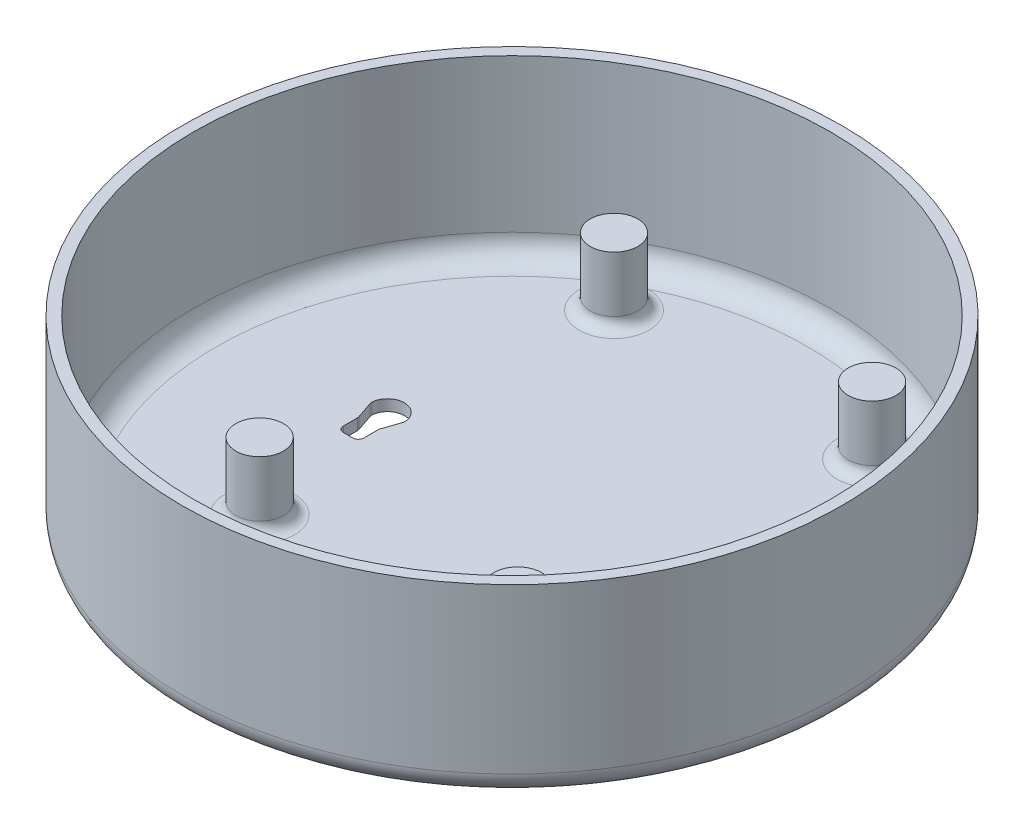
SolidWorks part; units mm, degrees
ref_plane "Front Plane" through (0, 0, 0) normal (0, 0, 1) x (1, 0, 0)
ref_plane "Top Plane" through (0, 0, 0) normal (0, 1, 0) x (1, 0, 0)
ref_plane "Right Plane" through (0, 0, 0) normal (1, 0, 0) x (0, 0, -1)
sketch "Sketch1" plane through (0, 0, 0) normal (0, 1, 0) x (1, 0, 0)
  circle A0 centre (0, 0) radius 29.527
  dimension "D1" = 59.054
extrude "Boss-Extrude1" add sketch "Sketch1" along normal blind 16.698
shell "Shell1" thickness 1 removed face at (0, 16.698, 29.527)
sketch "Sketch4" plane through (0, 0, 0) normal (0, -1, 0) x (1, 0, 0)
  line L0 (0, 29.527) -> (0, -29.527) construction
  line L1 (0, 0) -> (29.527, 0) construction
  line L2 (12.2635, -2.6139) -> (12.8385, -0.925)
  line L3 (15.2635, -2.6139) -> (14.6885, -0.925)
  line L4 (12.8385, -0.925) -> (12.8385, 0.925)
  line L5 (12.8385, 0.925) -> (14.6885, 0.925)
  line L6 (14.6885, 0.925) -> (14.6885, -0.925)
  line L7 (-14.6885, 0.925) -> (-14.6885, -0.925)
  line L8 (-12.8385, 0.925) -> (-14.6885, 0.925)
  line L9 (-12.8385, -0.925) -> (-12.8385, 0.925)
  line L10 (-15.2635, -2.6139) -> (-14.6885, -0.925)
  line L11 (-12.2635, -2.6139) -> (-12.8385, -0.925)
  arc A0 (12.2635, -2.6139) -> (15.2635, -2.6139) centre (13.7635, -2.6139) ccw
  circle A1 centre (0, 0) radius 29.527 construction
  arc A2 (-12.2635, -2.6139) -> (-15.2635, -2.6139) centre (-13.7635, -2.6139) cw
  point P21 (12.8385, 0)
  point P22 (14.7635, 0)
  dimension "D2" = 1.85
  dimension "D1" = 3
  dimension "D3" = 0.575
  dimension "D4" = 1.85
  dimension "D6" = 1.7841
extrude "Cut-Extrude2" cut sketch "Sketch4" against normal up to next
fillet "Fillet1" radius 0.5 12 edges at (15.2635, 0.5, -2.6139) (12.2635, 0.5, -2.6139) (12.8385, 0.5, -0.925) (14.6885, 0.5, -0.925) (14.6885, 0.5, 0.925) (12.8385, 0.5, 0.925) (-15.2635, 0.5, -2.6139) (-12.2635, 0.5, -2.6139) (-12.8385, 0.5, -0.925) (-14.6885, 0.5, -0.925) (-12.8385, 0.5, 0.925) (-14.6885, 0.5, 0.925)
fillet "Fillet2" radius 2 2 edges at (0, 0, 29.527) (0, 1, 28.527)
sketch "Sketch6" plane through (0, 1, 0) normal (0, 1, 0) x (1, 0, 0)
  line L0 (-11.56, -11.05) -> (-11.56, 20.7) construction
  line L1 (-11.56, 4.825) -> (7.4487, 4.8939) construction
  circle A0 centre (-11.56, 20.7) radius 2.1336
  circle A1 centre (-11.56, -11.05) radius 2.1336
  circle A2 centre (11.56, 20.7) radius 2.1336
  circle A3 centre (11.56, -11.05) radius 2.1336
  dimension "D1" = 2
  dimension "D3" = 20.7
  dimension "D4" = 11.56
  dimension "D2" = 2
extrude "Boss-Extrude3" add sketch "Sketch6" along normal blind 6
fillet "Fillet4" radius 1 4 edges at (-11.56, 1, 13.1836) (11.56, 1, 13.1836) (11.56, 1, -18.5664) (-11.56, 1, -18.5664)
sketch "Sketch7" plane through (0, 7, 0) normal (0, 1, 0) x (1, 0, 0)
  line L0 (11.56, 20.7) -> (11.56, -11.05) construction
  line L1 (11.56, 4.825) -> (-11.56, 4.825) construction
  line L2 (-11.56, 20.7) -> (-11.56, -11.05) construction
  line L3 (0, 20.7) -> (0, -11.05) construction
  line L4 (-11.56, 20.7) -> (11.56, 20.7) construction
  line L5 (11.56, -11.05) -> (-11.56, -11.05) construction
  circle A0 centre (-11.56, 20.7) radius 1.5126
  circle A1 centre (-11.56, 20.7) radius 2.1336 construction
